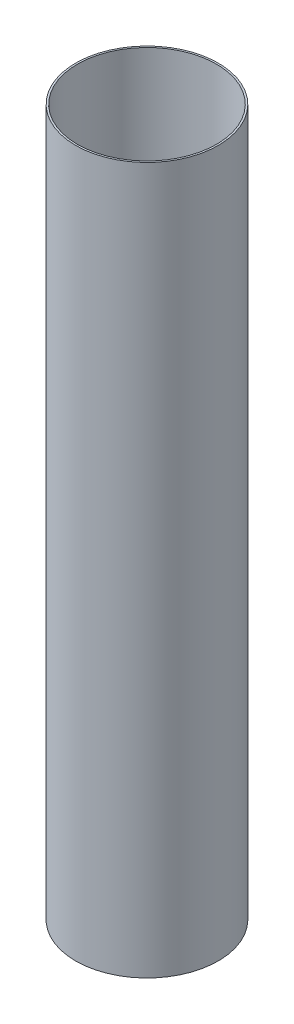
SolidWorks part; units mm, degrees
material "A-Glass Fiber"
ref_plane "Front Plane" through (0, 0, 0) normal (0, 0, 1) x (1, 0, 0)
ref_plane "Top Plane" through (0, 0, 0) normal (0, 1, 0) x (1, 0, 0)
ref_plane "Right Plane" through (0, 0, 0) normal (1, 0, 0) x (0, 0, -1)
sketch "Sketch1" plane through (0, 0, 0) normal (0, 0, 1) x (1, 0, 0)
  line L0 (78.16, 0) -> (78.16, 774)
  line L1 (76.2, 0) -> (76.2, 774)
  line L2 (78.16, 774) -> (76.2, 774)
  line L3 (76.2, 0) -> (78.16, 0)
  line L4 (0, 204.6154) -> (0, 85.8935) construction
  dimension "D1" = 76.2
  dimension "D2" = 774
  dimension "D3" = 1.96
revolve "Revolve1" add sketch "Sketch1" angle 360 about L4
